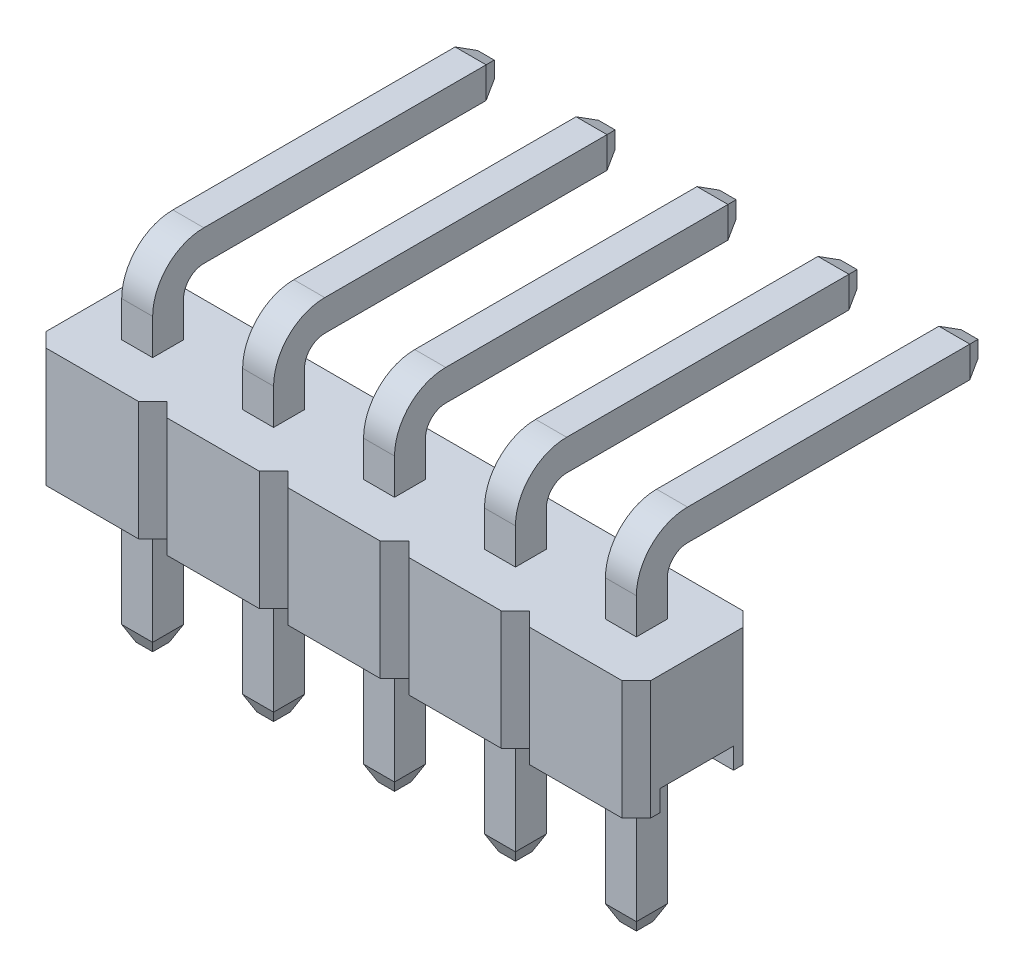
SolidWorks part; units mm, degrees
note: '?' marks a value the reader was unsure of.
ref_plane "Front" through (0, 0, 0) normal (0, 0, 1) x (1, 0, 0)
ref_plane "Top" through (0, 0, 0) normal (0, 1, 0) x (1, 0, 0)
ref_plane "Right" through (0, 0, 0) normal (1, 0, 0) x (0, 0, -1)
sketch "Sketch1" plane through (0, 0, 0) normal (0, 1, 0) x (1, 0, 0)
  line L0 (-1.27, 0.97) -> (-0.97, 1.27)
  line L1 (-0.97, -1.27) -> (0.97, -1.27)
  line L2 (-1.27, -0.97) -> (-1.27, 0.97)
  line L3 (-0.97, 1.27) -> (0.97, 1.27)
  line L4 (1.27, -0.97) -> (1.27, 0.97)
  line L5 (0.97, 1.27) -> (1.27, 0.97)
  line L6 (0.97, -1.27) -> (1.27, -0.97)
  line L7 (-1.27, -0.97) -> (-0.97, -1.27)
  point P0 (-1.27, -1.27)
  point P1 (1.27, 1.27)
  point P2 (-1.27, 1.27)
  point P3 (1.27, -1.27)
  point P12 (0, 1.27)
  point P14 (-1.27, 0)
  dimension "D1" = 0.3
  dimension "D2" = 45
  dimension "D3" = 0.3
  dimension "D4" = 45
  dimension "D5" = 0.3
  dimension "D6" = 45
  dimension "D7" = 0.3
  dimension "D8" = 45
  dimension "D9" = 2.54
extrude "Base" add sketch "Sketch1" along normal blind 2.5
pattern_linear "Base_Pattern" count 5 spacing 2.54 along (1, 0, 0) of "Base"
sketch "Sketch2" plane through (0, 0, 0) normal (1, 0, 0) x (0, 0, -1)
  line L1 (-0.77, 0) -> (0.77, 0)
  line L2 (-0.77, 0) -> (-0.77, 0.44)
  line L3 (-0.77, 0.44) -> (0.77, 0.44)
  line L4 (0.77, 0) -> (0.77, 0.44)
  point P4 (0, 0)
  dimension "D1" = 1.54
  dimension "D2" = 0.44
extrude "Cut" cut sketch "Sketch2" against normal through all and the other way through all
sketch "Sketch4" plane through (0, 0, 0) normal (1, 0, 0) x (0, 0, -1)
  line L0 (0, -3) -> (0, 3.25)
  line L1 (0.75, 4) -> (7, 4)
  arc A0 (0.75, 4) -> (0, 3.25) centre (0.75, 3.25) ccw
  dimension "D1" = 0.75
  dimension "D2" = 4
  dimension "D3" = 3
  dimension "D4" = 7
ref_plane "Plane1" through (0, -3, 0) normal (0, 1, 0) x (-1, 0, 0)
sketch "Sketch3" plane through (0, -3, 0) normal (0, 1, 0) x (1, 0, 0)
  line L1 (-0.325, -0.325) -> (0.325, -0.325)
  line L2 (-0.325, -0.325) -> (-0.325, 0.325)
  line L3 (-0.325, 0.325) -> (0.325, 0.325)
  line L4 (0.325, -0.325) -> (0.325, 0.325)
  point P4 (0, 0.325)
  point P6 (-0.325, 0)
  dimension "D1" = 0.65
sweep "Sweep1" add profiles "Sketch3" path "Sketch4"
chamfer "Pin Chamfer" distance 0.15 angle 65 4 edges at (0, -3, 0.325) (0.325, -3, 0) (0, -3, -0.325) (-0.325, -3, 0)
chamfer "Chamfer1" distance 0.15 angle 65 4 edges at (0, 3.675, -7) (0.325, 4, -7) (0, 4.325, -7) (-0.325, 4, -7)
pattern_linear "Pin Pattern" count 5 spacing 2.54 along (1, 0, 0) of "Pin Chamfer", "Sweep1", "Chamfer1"
ref_axis "Pin Axis" through (0, 5.6913, 0) along (0, -1, 0)?
